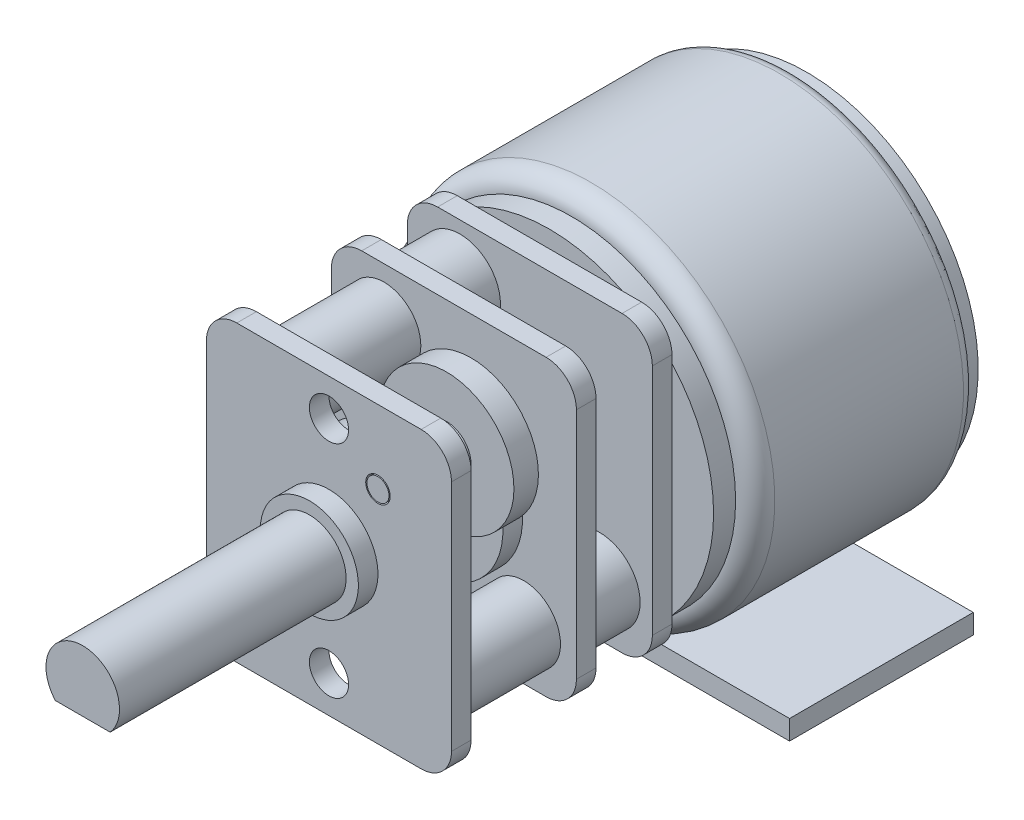
SolidWorks part; units mm, degrees
ref_plane "Front" through (0, 0, 0) normal (0, 0, 1) x (1, 0, 0)
ref_plane "Top" through (0, 0, 0) normal (0, 1, 0) x (1, 0, 0)
ref_plane "Right" through (0, 0, 0) normal (1, 0, 0) x (0, 0, -1)
sketch "Эскиз1" plane through (0, 0, 0) normal (0, 1, 0) x (1, 0, 0)
  line L0 (0, 0) -> (0, -39.2335) construction
  line L1 (0, 0) -> (-0.5, 0)
  line L3 (-0.75, -0.5) -> (-3, -0.5)
  line L4 (-3, -0.5) -> (-3, -1.5)
  line L5 (-3, -1.5) -> (-7, -1.5)
  line L6 (-7, -1.5) -> (-7, -2.1)
  line L8 (-7.5, -2.6) -> (-7.5, -10.3)
  line L10 (-6.7, -11.1) -> (-6.7, -12)
  line L11 (-6.7, -12) -> (-0.75, -12)
  line L12 (0, -12) -> (0, 0)
  line L14 (-7, -2.1) -> (-7, -2.6) construction
  line L15 (-6.7, -11.1) -> (-6.7, -10.3) construction
  line L16 (-6.7, -11.1) -> (-7.5, -11.1) construction
  line L18 (0, -21) -> (-2, -21)
  line L19 (-2, -21) -> (-2, -21.8)
  line L20 (-2, -21.8) -> (-1.5, -21.8)
  line L21 (-1.5, -21.8) -> (-1.5, -31.05)
  line L22 (-1.5, -31.05) -> (0, -31.05)
  line L24 (0, -21) -> (0, -31.05)
  line L25 (-0.75, -12) -> (-0.75, -13.75) construction
  line L26 (0, -14) -> (-0.5, -14) construction
  line L27 (-0.75, -0.5) -> (-0.75, -0.25)
  line L28 (0, -12) -> (-0.75, -12)
  arc A0 (-7, -2.1) -> (-7.5, -2.6) centre (-7, -2.6) ccw
  arc A1 (-7.5, -10.3) -> (-6.7, -11.1) centre (-6.7, -10.3) ccw
  arc A2 (-0.75, -13.75) -> (-0.5, -14) centre (-0.5, -13.75) ccw construction
  arc A3 (-0.5, 0) -> (-0.75, -0.25) centre (-0.5, -0.25) ccw
  dimension "D1" = 6
  dimension "D7" = 0.9
  dimension "D10" = 10.5
  dimension "D16" = 2
  dimension "D4" = 0.5
  dimension "D5" = 0.25
  dimension "D2" = 15
  dimension "D3" = 1
  dimension "D6" = 0.6
  dimension "D8" = 14
  dimension "D9" = 13.4
  dimension "D11" = 19.5
  dimension "D12" = 4
  dimension "D13" = 0.8
  dimension "D14" = 9.25
  dimension "D15" = 3
  dimension "D17" = 1.5
revolve "Motor" add sketch "Эскиз1" angle 360 about L0
sketch "Эскиз2" plane through (0, 0, 31.05) normal (0, 0, 1) x (1, 0, 0)
  line L0 (-1.118, -1) -> (1.118, -1)
  line L1 (-1.6853, 1.5) -> (1.9295, 1.5) construction
  arc A0 (1.118, -1) -> (-1.118, -1) centre (0, 0) ccw
  circle A1 centre (0, 0) radius 1.5 construction
  dimension "D1" = 2.5
extrude "Шпон-паз" cut sketch "Эскиз2" against normal blind 6.5 flip side to cut
sketch "Эскиз7" plane through (0, 0, 12) normal (0, 0, 1) x (1, 0, 0)
  line L1 (3.7627, 6) -> (-3.7627, 6)
  line L2 (5, 4.7627) -> (5, -4.7627)
  line L3 (3.7627, -6) -> (-3.7627, -6)
  line L4 (-5, 4.7627) -> (-5, -4.7627)
  line L5 (5, 6) -> (-5, -6) construction
  line L6 (5, -6) -> (-5, 6) construction
  arc A0 (-3.7627, 6) -> (-5, 4.7627) centre (-3.7627, 4.7627) ccw
  arc A1 (-5, -4.7627) -> (-3.7627, -6) centre (-3.7627, -4.7627) ccw
  arc A2 (3.7627, -6) -> (5, -4.7627) centre (3.7627, -4.7627) ccw
  arc A3 (5, 4.7627) -> (3.7627, 6) centre (3.7627, 4.7627) ccw
  point P0 (0, 0)
  point P18 (4.6376, -5.6376)
  point P19 (-4.6376, 5.6376)
  dimension "D3" = 14.6
  dimension "D4" = 1.2373
  dimension "D1" = 10
  dimension "D2" = 12
extrude "Бобышка-Вытянуть5" add sketch "Эскиз7" along normal blind 0.8
sketch "Эскиз8" plane through (0, 0, 21) normal (0, 0, -1) x (-1, 0, 0)
  line L0 (-5, -4.7627) -> (-5, -4.4598) construction
  line L1 (3.7627, 6) -> (-3.7627, 6)
  line L2 (5, 4.7627) -> (5, -4.7627)
  line L3 (3.7627, -6) -> (-3.7627, -6)
  line L4 (-5, 4.7627) -> (-5, -4.7627)
  line L5 (5, 6) -> (-5, -6) construction
  line L6 (5, -6) -> (-5, 6) construction
  line L7 (3.7627, -6) -> (2.9816, -6) construction
  line L8 (0, -4.5) -> (0, 4.5) construction
  line L9 (2, -3) -> (-2, 3) construction
  arc A0 (-3.7627, 6) -> (-5, 4.7627) centre (-3.7627, 4.7627) ccw
  arc A1 (-5, -4.7627) -> (-3.7627, -6) centre (-3.7627, -4.7627) ccw
  arc A2 (3.7627, -6) -> (5, -4.7627) centre (3.7627, -4.7627) ccw
  arc A3 (5, 4.7627) -> (3.7627, 6) centre (3.7627, 4.7627) ccw
  arc A4 (-5, -4.7627) -> (-3.7627, -6) centre (-3.7627, -4.7627) ccw construction
  circle A5 centre (0, -4.5) radius 0.8
  circle A6 centre (0, 4.5) radius 0.8
  circle A8 centre (2, -3) radius 0.5
  circle A9 centre (-2, 3) radius 0.5
  point P0 (0, 0)
  point P35 (2, -3)
  point P36 (-2, 3)
  dimension "D3" = 1
  dimension "D1" = 1.6
  dimension "D2" = 9
  dimension "D4" = 3
  dimension "D5" = 3
extrude "Бобышка-Вытянуть6" add sketch "Эскиз8" along normal blind 0.8
sketch "Эскиз9" plane through (0, 0, 12.8) normal (0, 0, 1) x (1, 0, 0)
  line L0 (4.5, -2.7511) -> (4.5, -4.8531) construction
  line L1 (2.0633, -5.5) -> (3.9242, -5.5) construction
  line L2 (5, -4.7627) -> (5, 4.7627) construction
  line L3 (-3.7627, -6) -> (3.7627, -6) construction
  line L4 (2.85, -3.85) -> (-2.85, 3.85) construction
  circle A0 centre (2.85, -3.85) radius 1.65
  circle A1 centre (-2.85, 3.85) radius 1.65
  point P14 (0, 0)
  dimension "D1" = 3.3
  dimension "D2" = 0.5
  dimension "D3" = 0.5
extrude "Бобышка-Вытянуть7" add sketch "Эскиз9" along normal blind 2.3
sketch "Эскиз10" plane through (0, 0, 15.1) normal (0, 0, 1) x (1, 0, 0)
  line L1 (3.7627, 6) -> (-3.7627, 6)
  line L2 (5, 4.7627) -> (5, -4.7627)
  line L3 (3.7627, -6) -> (1.2373, -6)
  line L4 (-5, 4.7627) -> (-5, -0.2627)
  line L5 (5, 6) -> (-5, -6) construction
  line L6 (5, -6) -> (-5, 6) construction
  line L8 (3.7627, 6) -> (2.9816, 6) construction
  line L9 (5, -4.7627) -> (5, -4.4598) construction
  line L10 (-3.7627, -1.5) -> (-1.2373, -1.5)
  line L11 (0, -4.7627) -> (0, -2.7373)
  arc A0 (-3.7627, 6) -> (-5, 4.7627) centre (-3.7627, 4.7627) ccw
  arc A2 (3.7627, -6) -> (5, -4.7627) centre (3.7627, -4.7627) ccw
  arc A3 (5, 4.7627) -> (3.7627, 6) centre (3.7627, 4.7627) ccw
  arc A4 (5, 4.7627) -> (3.7627, 6) centre (3.7627, 4.7627) ccw construction
  arc A5 (1.2373, -6) -> (0, -4.7627) centre (1.2373, -4.7627) cw
  arc A6 (-5, -0.2627) -> (-3.7627, -1.5) centre (-3.7627, -0.2627) ccw
  arc A7 (0, -2.7373) -> (-1.2373, -1.5) centre (-1.2373, -2.7373) ccw
  point P0 (0, 0)
  dimension "D1" = 5
  dimension "D2" = 7.5
extrude "Бобышка-Вытянуть8" add sketch "Эскиз10" along normal blind 0.8
sketch "Эскиз11" plane through (0, 0, 15.9) normal (0, 0, 1) x (1, 0, 0)
  circle A0 centre (2.85, -3.85) radius 1.5
  circle A1 centre (-2.85, 3.85) radius 1.5
  circle A4 centre (-2.85, 3.85) radius 1.65 construction
  circle A5 centre (2.85, -3.85) radius 1.65 construction
  dimension "D1" = 3
extrude "Бобышка-Вытянуть9" add sketch "Эскиз11" along normal up to next
sketch "Эскиз12" plane through (0, 0, 0) normal (0, 1, 0) x (1, 0, 0)
  line L0 (0, -20.2) -> (0, -12.8) construction
  line L1 (-1.35, -20.2) -> (-4.35, -20.2) construction
  line L2 (-4.5, -12.8) -> (-1.2, -12.8) construction
  line L3 (0, -20.2) -> (-0.5, -20.2)
  line L4 (-0.5, -20.2) -> (-0.5, -20)
  line L5 (-0.5, -20) -> (-3, -20)
  line L6 (-3, -20) -> (-3, -18.6)
  line L7 (-3, -18.6) -> (-0.5, -18.6)
  line L8 (-0.5, -18.6) -> (-0.5, -18.3)
  line L9 (-0.5, -18.3) -> (-1.5, -18.3)
  line L10 (-1.5, -18.3) -> (-1.5, -16.9)
  line L13 (-1.5, -16.9) -> (-3, -16.9)
  line L14 (-3, -16.9) -> (-3, -16.1)
  line L15 (-3, -16.1) -> (-0.5, -16.1)
  line L16 (-0.5, -16.1) -> (-0.5, -15.9)
  line L17 (-0.5, -15.9) -> (0, -15.9)
  line L18 (0, -15.9) -> (0, -20.2)
  line L19 (-4.35, -15.9) -> (-1.35, -15.9) construction
  line L21 (0, -12.8) -> (-0.75, -12.8)
  line L22 (-0.75, -12.8) -> (-0.75, -13)
  line L23 (-0.75, -13) -> (-1.5, -13)
  line L24 (-1.5, -13) -> (-1.5, -14)
  line L25 (-1.5, -14) -> (-0.75, -14)
  line L26 (-0.75, -14) -> (-0.75, -14.15)
  line L27 (-0.5, -14.4) -> (0, -14.4)
  line L28 (0, -14.4) -> (0, -12.8)
  arc A0 (-0.75, -14.15) -> (-0.5, -14.4) centre (-0.5, -14.15) ccw
  dimension "D8" = 1.5
  dimension "D10" = 0.25
  dimension "D1" = 1
  dimension "D2" = 0.2
  dimension "D3" = 1.4
  dimension "D4" = 0.8
  dimension "D5" = 1.4
  dimension "D6" = 3
  dimension "D7" = 6
  dimension "D9" = 1
  dimension "D11" = 3
  dimension "D12" = 1.6
revolve "Повернуть1" add sketch "Эскиз12" angle 360 about L0
ref_plane "Плоскость2" through (0, 0, 0) normal (-0.8321, 0.5547, 0) x (0, 0, 1)
sketch "Эскиз13" plane through (0, 0, 0) normal (-0.8321, 0.5547, 0) x (0, 0, 1)
  line L0 (21, -3.6056) -> (12.8, -3.6056)
  line L1 (12.8, -0.75) -> (12.8, 0.75) construction
  line L2 (21, -3.6056) -> (21, -3.1556)
  line L3 (21, -3.1556) -> (17.3, -3.1556)
  line L4 (17.3, -3.1556) -> (17.3, -2.6056)
  line L5 (17.3, -2.6056) -> (14, -2.6056)
  line L6 (14, -2.6056) -> (14, -0.8556)
  line L7 (14, -0.8556) -> (13, -0.8556)
  line L8 (13, -0.8556) -> (13, -3.305)
  line L9 (13, -3.305) -> (12.8, -3.305)
  line L10 (12.8, -3.305) -> (12.8, -3.6056)
  line L12 (21, -3.6056) -> (22.843, -3.6056) construction
  dimension "D1" = 0.9
  dimension "D2" = 2
  dimension "D3" = 5.5
  dimension "D4" = 0.2
  dimension "D5" = 1
  dimension "D6" = 3.3
revolve "Повернуть2" add sketch "Эскиз13" angle 360 about L12
sketch "Эскиз14" plane through (0, 0, 0) normal (-0.8321, 0.5547, 0) x (0, 0, 1)
  line L0 (21, 3.6056) -> (15.9, 3.6056)
  line L1 (15.9, -0.5) -> (15.9, 0.5) construction
  line L2 (21, 3.6056) -> (21.7209, 3.6056) construction
  line L3 (21, 3.6056) -> (21, 3.1556)
  line L4 (21, 3.1556) -> (20, 3.1556)
  line L5 (20, 3.1556) -> (20, 2.6056)
  line L6 (20, 2.6056) -> (18.2, 2.6056)
  line L7 (18.2, 2.6056) -> (18.2, 0.8556)
  line L8 (18.2, 0.8556) -> (17.2, 0.8556)
  line L9 (17.2, 0.8556) -> (17.2, 3.1056)
  line L10 (17.2, 3.1056) -> (15.9, 3.1056)
  line L11 (15.9, 3.1056) -> (15.9, 3.6056)
  line L12 (20.2, 6.7363) -> (20.2, -1.1893) construction
  line L13 (15.9, -1.1893) -> (15.9, 6.7363) construction
  dimension "D1" = 0.9
  dimension "D2" = 1
  dimension "D3" = 2
  dimension "D4" = 5.5
  dimension "D5" = 0.2
  dimension "D6" = 2
  dimension "D7" = 1.3
revolve "Повернуть3" add sketch "Эскиз14" angle 360 about L2
ref_plane "Плоскость1" through (0, -7.5, 0) normal (0, -1, 0) x (-1, 0, 0)
sketch "Эскиз4" plane through (0, -7.5, 0) normal (0, -1, 0) x (-1, 0, 0)
  line L0 (0, -2.6) -> (0, -10.3) construction
  line L1 (3.5, -10.2) -> (-8, -10.2)
  line L2 (3.5, -10.2) -> (3.5, -2.7)
  line L3 (3.5, -2.7) -> (-8, -2.7)
  line L4 (-8, -10.2) -> (-8, -2.7)
  line L5 (3.5, -6.45) -> (-8, -6.45) construction
  line L7 (7.5, -10.3) -> (-7.5, -10.3) construction
  line L8 (7.5, -2.6) -> (-7.5, -2.6) construction
  point P5 (0, -6.45)
  dimension "D1" = 7.5
  dimension "D2" = 11.5
  dimension "D3" = 3.5
extrude "Плата" add sketch "Эскиз4" along normal blind 0.8 separate body
sketch "Пайка контактов" plane through (0, -8.3, 0) normal (0, -1, 0) x (1, 0, 0)
  line L0 (-0.75, 7.2) -> (2.25, 7.2) construction
  line L1 (0.75, 5.7) -> (-2.25, 5.7) construction
  line L2 (-0.75, 5.7) -> (-0.75, 7.2) construction
  line L3 (0, 2.6) -> (0, 10.3) construction
  line L5 (-0.75, 7.2) -> (0.75, 5.7) construction
  line L6 (-7.5, 10.3) -> (7.5, 10.3) construction
  line L7 (-7.5, 2.6) -> (7.5, 2.6) construction
  line L8 (7, 5.5333) -> (7, 3.7) construction
  line L9 (7, 7.3667) -> (7, 5.5333) construction
  line L10 (7, 7.3667) -> (7, 9.2) construction
  line L11 (7, 6.45) -> (8, 6.45) construction
  line L12 (8, 2.7) -> (8, 10.2) construction
  circle A0 centre (-2.25, 5.7) radius 0.75
  circle A1 centre (-0.75, 7.2) radius 0.75
  circle A2 centre (0.75, 5.7) radius 0.75
  circle A3 centre (2.25, 7.2) radius 0.75
  circle A4 centre (7, 3.7) radius 0.75
  circle A5 centre (7, 5.5333) radius 0.75
  circle A6 centre (7, 7.3667) radius 0.75
  circle A7 centre (7, 9.2) radius 0.75
  point P13 (0, 6.45)
  point P29 (8, 6.45)
  dimension "D1" = 1.5
  dimension "D4" = 1.5
  dimension "D2" = 3
  dimension "D3" = 1.5
  dimension "D5" = 5.5
  dimension "D6" = 1
extrude "Пайка" add sketch "Пайка контактов" along normal blind 0.7 draft 35
sketch "Эскиз6" plane through (0, -8.3, 0) normal (0, -1, 0) x (1, 0, 0)
  line L0 (5.7717, 10.2) -> (5.7717, 2.7) construction
  line L1 (8, 10.2) -> (-3.5, 10.2) construction
  line L2 (-3.5, 2.7) -> (8, 2.7) construction
  line L3 (-3.5, 8.1932) -> (8, 8.1932) construction
  line L4 (-3.5, 10.2) -> (-3.5, 2.7) construction
  line L5 (8, 2.7) -> (8, 10.2) construction
  text T0 "B1 B2 A1 A2" font "Century Gothic" height 0.85
  text T1 " B1 A2 B2 A1" font "Century Gothic" height 0.8
extrude "Надписи" add sketch "Эскиз6" along normal blind 0.01
